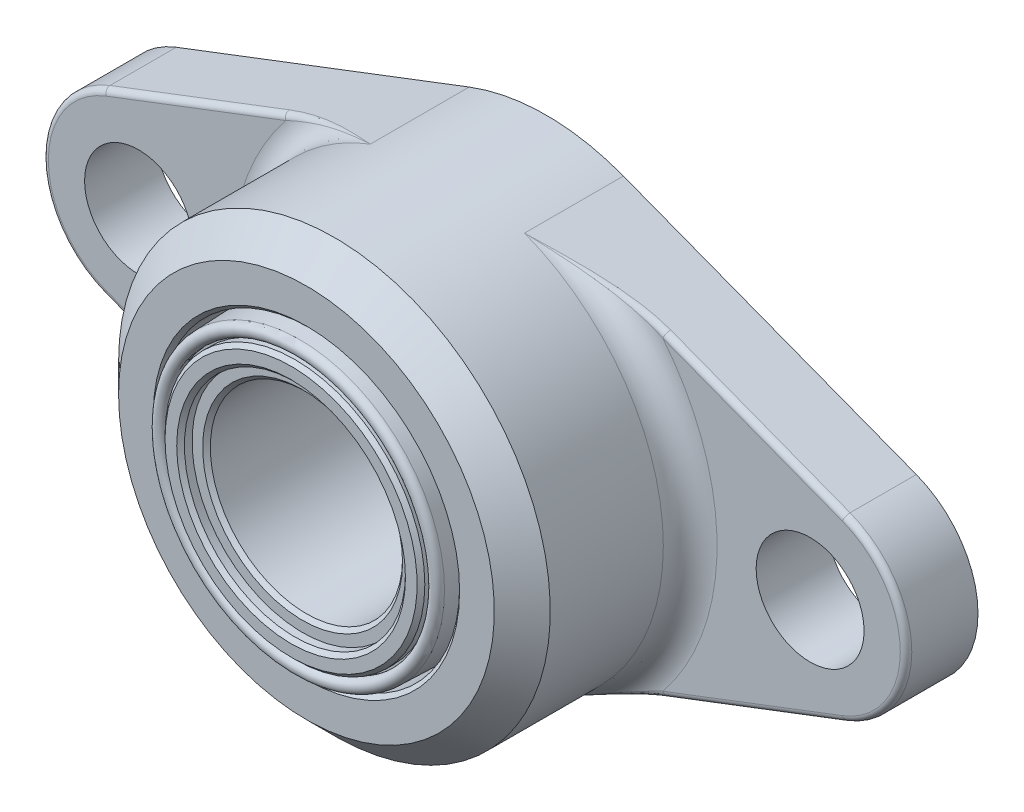
SolidWorks part; units mm, degrees
ref_plane "Front Plane" through (0, 0, 0) normal (0, 0, 1) x (1, 0, 0)
ref_plane "Top Plane" through (0, 0, 0) normal (0, 1, 0) x (1, 0, 0)
ref_plane "Right Plane" through (0, 0, 0) normal (1, 0, 0) x (0, 0, -1)
sketch "Sketch1" plane through (0, 0, 0) normal (0, 0, 1) x (1, 0, 0)
  line L0 (-22.225, 0) -> (22.225, 0) construction
  line L1 (0, 14.2875) -> (0, -14.2875) construction
  line L2 (-24.4929, 5.9312) -> (-5.1027, 13.3452)
  line L3 (5.1027, 13.3452) -> (24.4929, 5.9312)
  line L4 (24.4929, -5.9312) -> (5.1027, -13.3452)
  line L5 (-24.4929, -5.9312) -> (-5.1027, -13.3452)
  line L6 (-28.575, 0) -> (28.575, 0) construction
  line L7 (4.4991, 4.4991) -> (10.1028, 10.1028) construction
  circle A0 centre (-22.225, 0) radius 3.5719
  circle A1 centre (22.225, 0) radius 3.5719
  circle A2 centre (0, 0) radius 14.2875
  arc A3 (-24.4929, 5.9312) -> (-24.4929, -5.9312) centre (-22.225, 0) ccw
  arc A4 (24.4929, -5.9312) -> (24.4929, 5.9312) centre (22.225, 0) ccw
  circle A5 centre (0, 0) radius 6.3627
  circle A6 centre (0, 0) radius 9.8848 construction
  point P23 (6.9896, 6.9896)
  point P24 (0, 9.8848)
  point P25 (0, 6.3627)
  dimension "Mounting Hole" = 7.1437
  dimension "ID" = 12.7254
  dimension "D4" = 19.7697
  dimension "Mounting Center" = 44.45
  dimension "Height" = 28.575
  dimension "Length" = 57.15
  dimension "D2" = 45
  dimension "D3" = 7.9248
  dimension "D1" = 3.5221
sketch "Sketch2" plane through (0, 0, 0) normal (1, 0, 0) x (0, 0, -1)
  line L0 (7.9375, 0) -> (-7.9375, 0) construction
  point P2 (3.175, 0)
  point P4 (7.9375, 0)
  dimension "Width" = 15.875
  dimension "flange thickness" = 4.7625
  dimension "Bearing Width" = 15.875
sketch "Sketch3" plane through (0, 0, 0) normal (0, 0, 1) x (1, 0, 0)
  line L0 (-24.4929, 5.9312) -> (-5.1027, 13.3452) construction
  line L1 (5.1027, 13.3452) -> (24.4929, 5.9312) construction
  line L2 (24.4929, -5.9312) -> (5.1027, -13.3452) construction
  line L3 (-24.4929, -5.9312) -> (-5.1027, -13.3452) construction
  line L4 (-24.4929, 5.9312) -> (-5.1027, 13.3452)
  line L5 (5.1027, 13.3452) -> (24.4929, 5.9312)
  line L6 (24.4929, -5.9312) -> (5.1027, -13.3452)
  line L7 (-24.4929, -5.9312) -> (-5.1027, -13.3452)
  arc A0 (-24.4929, 5.9312) -> (-24.4929, -5.9312) centre (-22.225, 0) ccw construction
  circle A1 centre (-22.225, 0) radius 3.5719 construction
  circle A2 centre (0, 0) radius 14.2875 construction
  circle A3 centre (22.225, 0) radius 3.5719 construction
  arc A4 (24.4929, -5.9312) -> (24.4929, 5.9312) centre (22.225, 0) ccw construction
  arc A5 (-24.4929, 5.9312) -> (-24.4929, -5.9312) centre (-22.225, 0) ccw
  circle A6 centre (-22.225, 0) radius 3.5719
  arc A7 (-5.1027, -13.3452) -> (5.1027, -13.3452) centre (0, 0) ccw
  circle A8 centre (22.225, 0) radius 3.5719
  arc A9 (24.4929, -5.9312) -> (24.4929, 5.9312) centre (22.225, 0) ccw
  circle A10 centre (0, 0) radius 9.8848 construction
  circle A11 centre (0, 0) radius 9.8848
  arc A12 (5.1027, 13.3452) -> (-5.1027, 13.3452) centre (0, 0) ccw
extrude "Boss-Extrude1" add sketch "Sketch3" along normal up to vertex (-3.175 mm away) from vertex at -7.9375 starting at point (0, 0, -7.9375)
sketch "Sketch4" plane through (0, 0, -3.175) normal (0, 0, 1) x (1, 0, 0)
  circle A0 centre (0, 0) radius 14.2875 construction
  circle A1 centre (0, 0) radius 9.8848 construction
  circle A2 centre (0, 0) radius 14.2875
  circle A3 centre (0, 0) radius 9.8848
extrude "Boss-Extrude2" add sketch "Sketch4" along normal up to vertex (11.1125 mm away) up to point (0, 0, 7.9375)
chamfer "Chamfer1" distance 0.254 angle 45 2 edges at (9.8848, 0, 7.9375) (9.8848, 0, -7.9375)
fillet "Fillet1" radius 1.778 2 edges
fillet "Fillet2" radius 0.381 10 edges at (8.643, 11.9916, -2.6271) (28.575, 0, -3.175) (-8.643, 11.9916, -2.6271) (-28.575, 0, -3.175) (-8.643, -11.9916, -2.6271) (8.643, -11.9916, -2.6271)
chamfer "Chamfer2" distance 1.8521 angle 45 1 edges at (14.2875, 0, 7.9375)
sketch "Sketch5" plane through (0, 0, 0) normal (1, 0, 0) x (0, 0, -1)
  line L0 (-7.9375, 6.3627) -> (7.9375, 6.3627)
  line L1 (-7.9375, 6.3627) -> (-7.9375, 9.8848)
  line L2 (-7.9375, 9.8848) -> (7.9375, 9.8848)
  line L3 (7.9375, 9.8848) -> (7.9375, 6.3627)
  line L4 (-7.9375, 0) -> (7.9375, 0) construction
  dimension "D1" = 15.875
sketch "Sketch6" plane through (0, 0, 0) normal (1, 0, 0) x (0, 0, -1)
  line L0 (0, 9.8848) -> (-8.3891, 9.5919)
  line L1 (-8.1915, 8.7594) -> (-8.1915, 8.5979)
  line L2 (-8.1915, 8.5979) -> (-8.9535, 8.5979)
  line L3 (-8.9535, 8.5979) -> (-8.9535, 7.3171)
  line L4 (-8.1915, 6.3627) -> (-8.1915, 7.3171)
  line L5 (-8.1915, 7.3171) -> (-8.9535, 7.3171)
  line L6 (-7.9375, 6.3627) -> (7.9375, 6.3627) construction
  line L7 (-7.9375, 6.3627) -> (-7.9375, 9.8848) construction
  line L8 (-7.9375, 12.4354) -> (-7.9375, -12.4354) construction
  line L9 (-7.9375, 9.8848) -> (7.9375, 9.8848) construction
  line L10 (7.8899, 6.3627) -> (7.8899, 7.3171)
  line L11 (7.8899, 7.3171) -> (8.6519, 7.3171)
  line L12 (8.6519, 7.3171) -> (8.6519, 8.5979)
  line L13 (8.6519, 8.5979) -> (6.1119, 8.5979)
  line L14 (6.1119, 8.5979) -> (6.1119, 8.7594)
  line L15 (6.1119, 8.7594) -> (7.9375, 8.7594)
  line L16 (7.9375, 9.8848) -> (7.9375, 6.3627) construction
  line L17 (7.9375, 8.7594) -> (7.9375, 9.8848)
  line L18 (-8.1915, 6.3627) -> (7.8899, 6.3627)
  line L19 (0, 9.8848) -> (7.9375, 9.8848)
  line L20 (-7.9375, 0) -> (7.9375, 0) construction
  arc A0 (-8.3891, 9.5919) -> (-8.1915, 8.7594) centre (-8.3738, 9.1558) ccw
  dimension "D1" = 1.016
  dimension "D2" = 0.254
  dimension "D3" = 2
  dimension "D4" = 3.5221
  dimension "D5" = 1.2808
  dimension "D6" = 14.6342
  dimension "D7" = 0.8325
  dimension "D8" = 0.7144
  dimension "D9" = 2.54
revolve "Revolve1" add sketch "Sketch6" angle 360 about L20
chamfer "Chamfer3" distance 0.254 angle 45 6 edges at (7.3171, 0, -8.6519) (8.5979, 0, -8.6519) (8.5979, 0, 8.9535) (7.3171, 0, 8.9535) (6.3627, 0, 8.1915) (6.3627, 0, -7.8899)
equation "\"D1@Chamfer2\"=(\"Width@Sketch2\"-\"flange thickness@Sketch2\")/6"
equation "\"D1@Sketch1\"=\"D3@Sketch1\"/2.25"
equation "\"D1@Sketch5\"=\"Bearing Width@Sketch2\""
equation "\"D5@Sketch6\"=\"D4@Sketch6\"/2.75"
equation "\"D6@Sketch6\"=\"ID@Sketch1\"*1.15"
equation "\"D7@Sketch6\"=\"D5@Sketch6\"*.65"
